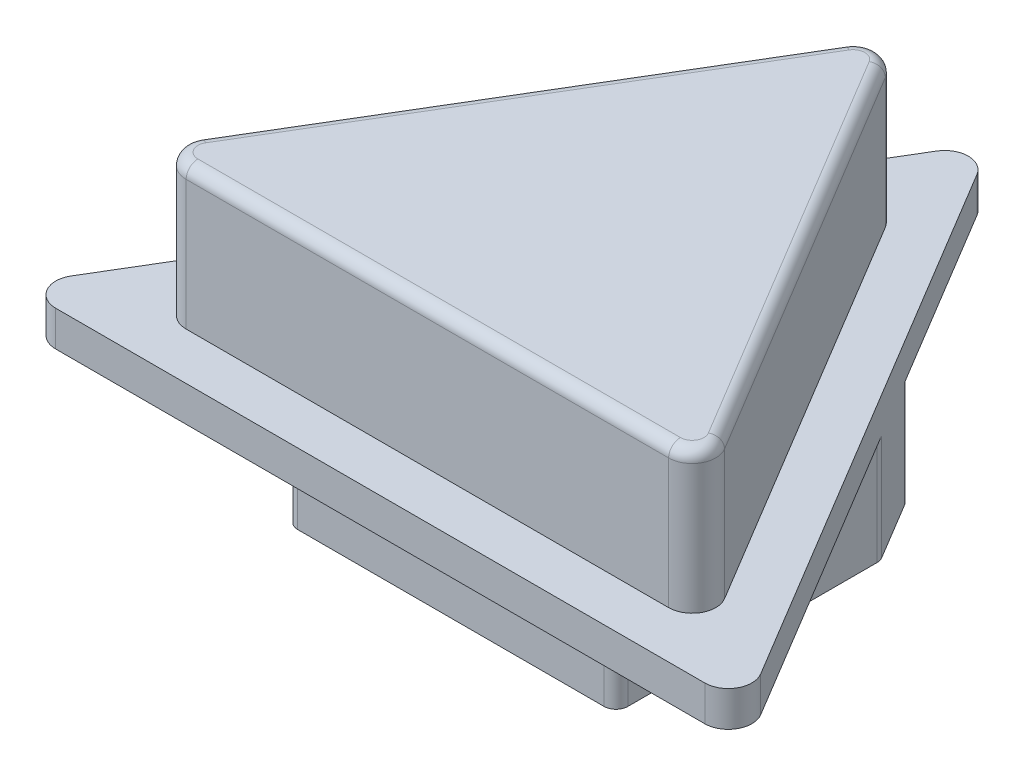
SolidWorks part; units mm, degrees
ref_plane "Front Plane" through (0, 0, 0) normal (0, 0, 1) x (1, 0, 0)
ref_plane "Top Plane" through (0, 0, 0) normal (0, 1, 0) x (1, 0, 0)
ref_plane "Right Plane" through (0, 0, 0) normal (1, 0, 0) x (0, 0, -1)
sketch "Sketch1" plane through (0, 0, 0) normal (0, 1, 0) x (1, 0, 0)
  line L0 (0, 0) -> (6, 10)
  line L1 (6, 10) -> (12, 0)
  line L2 (12, 0) -> (0, 0)
  point P3 (6, 0)
  dimension "D1" = 12
  dimension "D2" = 10
extrude "Boss-Extrude1" add sketch "Sketch1" along normal blind 3
sketch "Sketch2" plane through (0, 0, 0) normal (0, -1, 0) x (1, 0, 0)
  line L12 (13.7662, 1) -> (-1.7662, 1)
  line L13 (-1.7662, 1) -> (6, -11.9437)
  line L14 (6, -11.9437) -> (13.7662, 1)
  line L15 (13.7662, 1) -> (-1.7662, 1)
  line L16 (-1.7662, 1) -> (6, -11.9437)
  line L17 (6, -11.9437) -> (13.7662, 1)
  dimension "D1" = 1
extrude "Boss-Extrude2" add sketch "Sketch2" along normal blind 0.75
sketch "Sketch3" plane through (0, -0.75, 0) normal (0, -1, 0) x (1, 0, 0)
  line L0 (13.7662, 1) -> (-1.7662, 1) construction
  line L1 (8.5, -1.5) -> (3.5, -1.5)
  line L2 (8.5, -1.5) -> (8.5, -6.5)
  line L3 (8.5, -6.5) -> (3.5, -6.5)
  line L4 (3.5, -1.5) -> (3.5, -6.5)
  line L5 (8.5, -1.5) -> (3.5, -6.5) construction
  line L6 (8.5, -6.5) -> (3.5, -1.5) construction
  line L7 (9.5, -7.5) -> (2.5, -7.5)
  line L8 (2.5, -0.5) -> (2.5, -7.5)
  line L9 (9.5, -0.5) -> (2.5, -0.5)
  line L10 (9.5, -0.5) -> (9.5, -7.5)
  line L11 (-1.7662, 1) -> (6, -11.9437) construction
  line L12 (6, -11.9437) -> (13.7662, 1) construction
  line L13 (-1.7662, 1) -> (6, -11.9437)
  line L14 (6, -11.9437) -> (13.7662, 1)
  point P0 (6, -4)
  point P8 (6, 1)
  line M1 (6, -11.9437) -> (13.7662, 1)
  line M3 (-1.7662, 1) -> (6, -11.9437)
  dimension "D1" = 5
  dimension "D2" = 5
  dimension "D4" = 5
  dimension "D3" = 1
extrude "Boss-Extrude3" add sketch "Sketch3" along normal blind 2.25 contours L10 L9 L8 L7 L4 L1 L2 L3 M3 M1 region at (6, -0.75, -7.401)
fillet "Fillet1" radius 0.5 3 edges at (6, -0.375, -11.9437) (-1.7662, -0.375, 1) (13.7662, -0.375, 1)
fillet "Fillet2" radius 0.5 3 edges at (0, 1.5, 0) (12, 1.5, 0) (6, 1.5, -10)
fillet "Fillet4" radius 0.25 6 edges at (6, 3, -9.5282) (8.9872, 3, -5.0213) (11.552, 3, -0.2537) (6, 3, 0) (0.448, 3, -0.2537) (3.0128, 3, -5.0213)
fillet "Fillet6" radius 0.25 6 edges at (2.5, -1.875, -0.5) (2.5, -1.875, -6.1103) (3.3338, -1.875, -7.5) (8.6662, -1.875, -7.5) (9.5, -1.875, -6.1103) (9.5, -1.875, -0.5)
